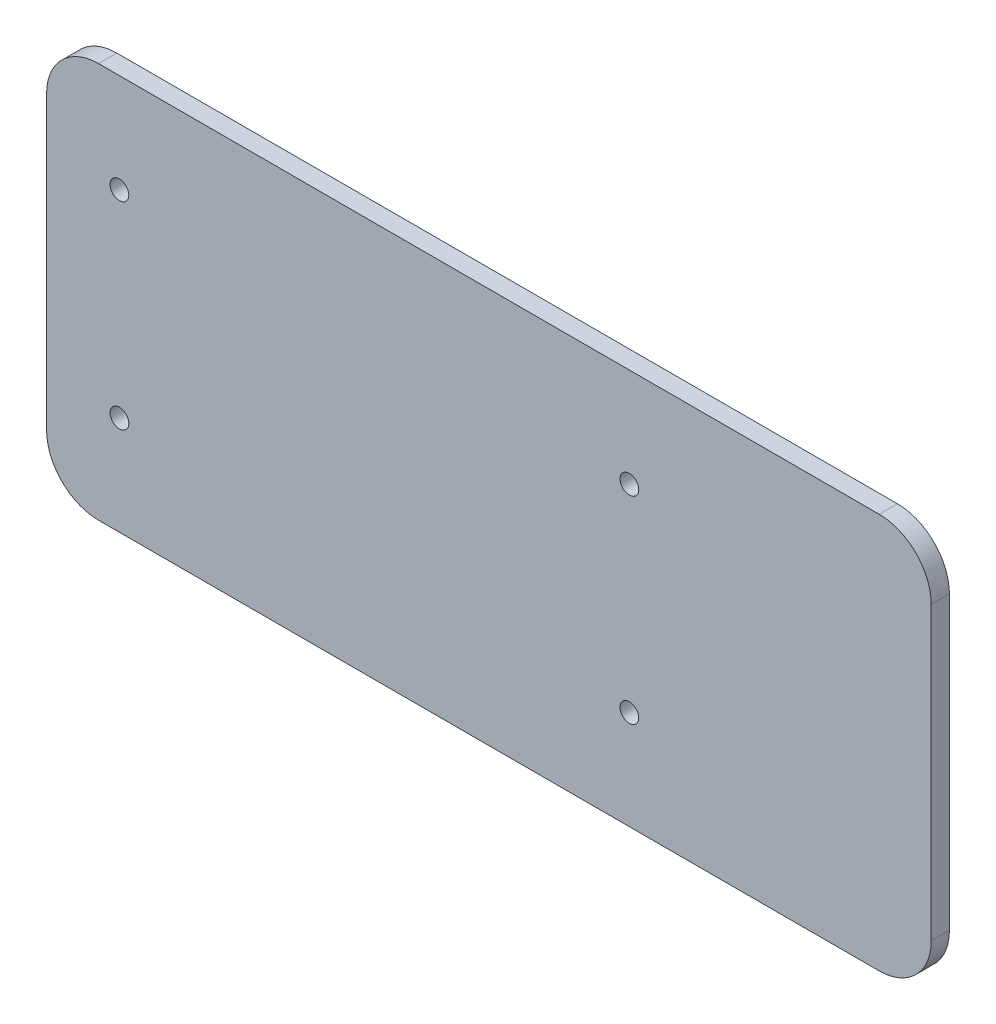
SolidWorks part; units mm, degrees
material "3d打印 35%"
ref_plane "前视基准面" through (0, 0, 0) normal (0, 0, 1) x (1, 0, 0)
ref_plane "上视基准面" through (0, 0, 0) normal (0, 1, 0) x (1, 0, 0)
ref_plane "右视基准面" through (0, 0, 0) normal (1, 0, 0) x (0, 0, -1)
sketch "草图1" plane through (0, 0, 0) normal (0, 0, 1) x (1, 0, 0)
  line L1 (-85, 38) -> (85, 38)
  line L2 (-85, 38) -> (-85, -38)
  line L3 (-85, -38) -> (85, -38)
  line L4 (85, 38) -> (85, -38)
  line L5 (-85, 38) -> (85, -38) construction
  line L6 (-85, -38) -> (85, 38) construction
  point P0 (0, 0)
extrude "凸台-拉伸1" add sketch "草图1" along normal blind 3.5
fillet "圆角1" radius 10 4 edges at (-85, 38, 1.75) (-85, -38, 1.75) (85, -38, 1.75) (85, 38, 1.75)
ref_plane "基准面4" through (0, 0, 0) normal (0, 1, 0) x (1, 0, 0)
ref_axis "基准轴1" through (-85, 0, 0) along (1, 0, 0)
sketch "草图2" plane through (0, 0, 0) normal (0, 0, -1) x (-1, 0, 0)
  line L0 (1.925, 0) -> (-1.925, 0) construction
  line L1 (-23, 10) -> (-31, 10)
  line L2 (-23, 10) -> (-23, -10)
  line L3 (-23, -10) -> (-31, -10)
  line L4 (-31, 10) -> (-31, -10)
  line L5 (-23, 10) -> (-31, -10) construction
  line L6 (-23, -10) -> (-31, 10) construction
  line L7 (-85, -28) -> (-85, 28) construction
  point P0 (-27, 0)
  dimension "D1" = 54
extrude "切除-拉伸1" cut sketch "草图2" against normal blind 3
sketch "草图3" plane through (0, 0, 0) normal (0, 0, -1) x (-1, 0, 0)
  line L0 (1.925, 0) -> (-1.925, 0) construction
  line L1 (75, 10) -> (67, 10)
  line L2 (75, 10) -> (75, -10)
  line L3 (75, -10) -> (67, -10)
  line L4 (67, 10) -> (67, -10)
  line L5 (75, 10) -> (67, -10) construction
  line L6 (75, -10) -> (67, 10) construction
  line L7 (85, 28) -> (85, -28) construction
  point P0 (71, 0)
  dimension "D1" = 10
extrude "切除-拉伸2" cut sketch "草图3" against normal blind 3
ref_plane "基准面5" through (-71, 0, 0) normal (1, 0, 0) x (0, 0, -1)
ref_axis "基准轴3" through (-71, -24.6699, 0) along (0, 1, 0)
sketch "草图6" plane through (0, 0, 0) normal (0, 0, -1) x (-1, 0, 0)
  line L0 (71, 1.65) -> (71, -1.65) construction
  line L1 (1.925, 0) -> (-1.925, 0) construction
  circle A0 centre (71, -19) radius 1.8
  dimension "D1" = 19
extrude "切除-拉伸4" cut sketch "草图6" against normal blind 4
mirror "镜向1" about plane through (0, 0, 0) normal (0, 1, 0) of "切除-拉伸4"
ref_plane "基准面6" through (-22, 0, 0) normal (1, 0, 0) x (0, 0, -1)
mirror "镜向2" about plane through (-22, 0, 0) normal (1, 0, 0) of "镜向1", "切除-拉伸4"
